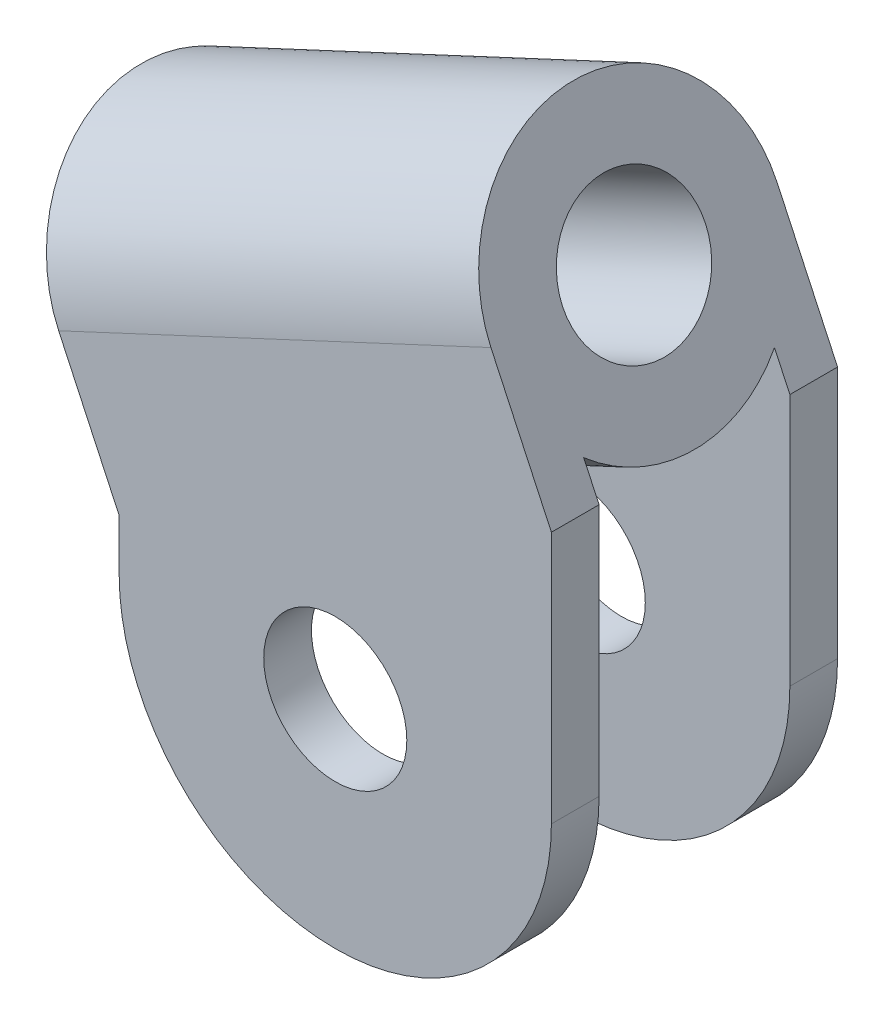
SolidWorks part; units mm, degrees
ref_plane "Front Plane" through (0, 0, 0) normal (0, 0, 1) x (1, 0, 0)
ref_plane "Top Plane" through (0, 0, 0) normal (0, 1, 0) x (1, 0, 0)
ref_plane "Right Plane" through (0, 0, 0) normal (1, 0, 0) x (0, 0, -1)
sketch "Sketch1" plane through (0, 0, 0) normal (0, 0, 1) x (1, 0, 0)
  line L0 (0, 0) -> (90.6308, 42.2618)
  line L1 (90.6308, 42.2618) -> (77.9522, 69.4511)
  line L2 (77.9522, 69.4511) -> (-12.6785, 27.1892)
  line L3 (-12.6785, 27.1892) -> (0, 0)
  line L4 (-85.5364, 0) -> (85.5364, 0) construction
  point P7 (0, 0)
  dimension "D1" = 25
  dimension "D2" = 30
  dimension "D3" = 100
revolve "Revolve1" add sketch "Sketch1" angle 360 about L0
sketch "Sketch2" plane through (0, 0, 0) normal (0, 0, 1) x (1, 0, 0)
  line L0 (12.6785, -27.1892) -> (12.6785, -37.8883)
  line L1 (103.3093, -37.8883) -> (103.3093, 15.0726)
  line L2 (12.6785, -27.1892) -> (103.3093, 15.0726)
  arc A0 (12.6785, -37.8883) -> (103.3093, -37.8883) centre (57.9939, -37.8883) ccw
extrude "Boss-Extrude1" add sketch "Sketch2" along normal blind 10 from offset 20 separate body contours L0 A0 L1 L2 region at (62.7282, -39.4235, 0)
extrude "Boss-Extrude2" add sketch "Sketch2<3>" against normal blind 10 from offset 20 separate body offset against normal yes
sketch "Sketch2<3>" plane through (0, 0, 0) normal (0, 0, 1) x (1, 0, 0) same geometry as "Sketch2"
sketch "Sketch3" plane through (12.6785, -27.1892, 0) normal (-0.4226, 0.9063, 0) x (0.9063, 0.4226, 0)
  line L4 (100, -20) -> (0, -20)
  line L5 (0, -20) -> (0, -30)
  line L6 (0, -30) -> (100, -30)
  line L7 (100, -30) -> (100, -20)
  line L8 (100, -20) -> (0, -20)
  line L9 (0, -20) -> (0, -30)
  line L10 (0, -30) -> (100, -30)
  line L11 (100, -30) -> (100, -20)
  line L12 (0, 20) -> (100, 20)
  line L13 (100, 20) -> (100, 30)
  line L14 (100, 30) -> (0, 30)
  line L15 (0, 30) -> (0, 20)
  line L16 (0, 20) -> (100, 20)
  line L17 (100, 20) -> (100, 30)
  line L18 (100, 30) -> (0, 30)
  line L19 (0, 30) -> (0, 20)
  dimension "D1" = 0
  dimension "D2" = 0
extrude "Boss-Extrude3" add sketch "Sketch3" along normal up to surface (30 mm away) up to face at (12.6785, -27.1892, 0)
sketch "Sketch4" plane through (90.6308, 42.2618, 0) normal (0.9063, 0.4226, 0) x (0, 0, -1)
  circle A0 centre (0, 0) radius 15
  dimension "D1" = 30
extrude "Cut-Extrude1" cut sketch "Sketch4" against normal through all both and the other way through all
sketch "Sketch5" plane through (0, 0, 30) normal (0, 0, 1) x (1, 0, 0)
  circle A0 centre (57.9939, -37.8883) radius 15
  dimension "D1" = 30
extrude "Cut-Extrude2" cut sketch "Sketch5" against normal through all both and the other way through all
